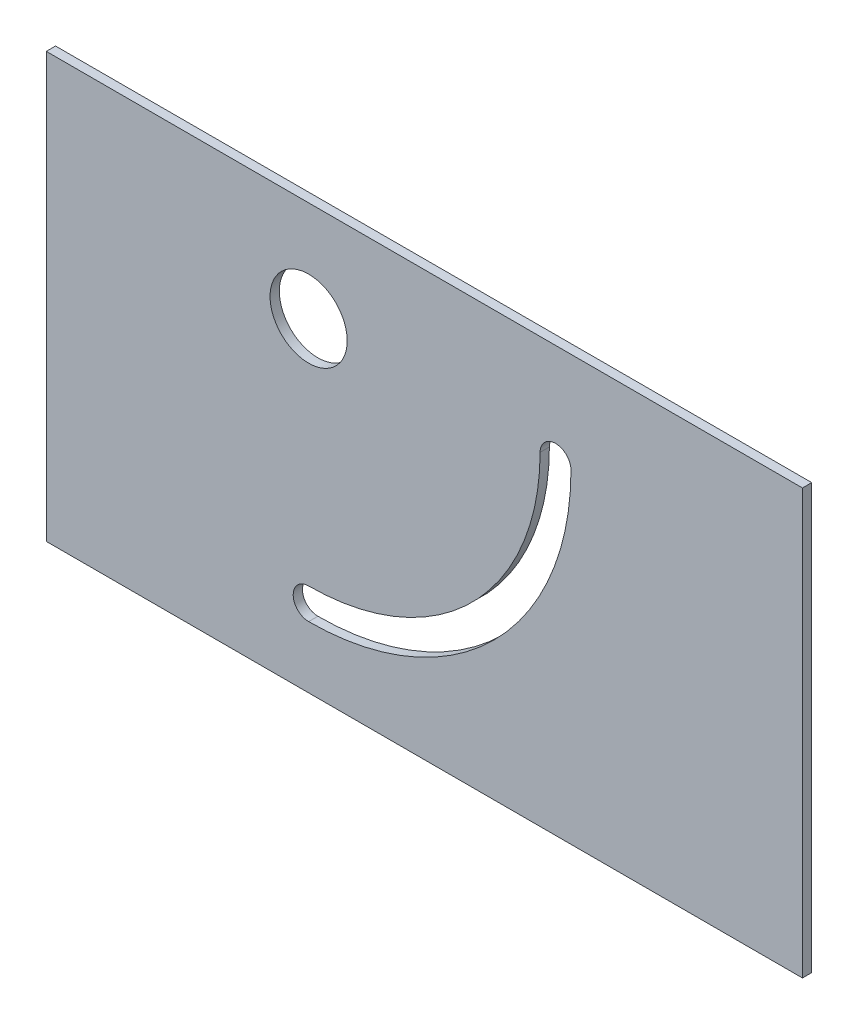
SolidWorks part; units mm, degrees
material "birch 3mm plywood"
ref_plane "Front Plane" through (0, 0, 0) normal (0, 0, 1) x (1, 0, 0)
ref_plane "Top Plane" through (0, 0, 0) normal (0, 1, 0) x (1, 0, 0)
ref_plane "Right Plane" through (0, 0, 0) normal (1, 0, 0) x (0, 0, -1)
sketch "Sketch1" plane through (0, 0, 0) normal (0, 0, 1) x (1, 0, 0)
  line L1 (-0.5, 137.5) -> (244.5, 137.5)
  line L2 (-0.5, 137.5) -> (-0.5, 0)
  line L3 (-0.5, 0) -> (244.5, 0)
  line L4 (244.5, 137.5) -> (244.5, 0)
  line L5 (84.5, 59.75) -> (84.5, -77.75) construction
  arc A3 (169.5, 105) -> (159.5, 105) centre (164.5, 105) ccw
  arc A4 (159.5, 105) -> (84.5, 30) centre (84.5, 105) cw
  arc A5 (169.5, 105) -> (84.5, 20) centre (84.5, 105) cw
  arc A6 (84.5, 20) -> (84.5, 30) centre (84.5, 25) cw
  circle A7 centre (84.5, 105) radius 12.5
  dimension "D1" = 10
  dimension "D2" = 75
  dimension "D3" = 20
  dimension "D7" = 25
  dimension "D4" = 20
  dimension "D5" = 85
  dimension "D6" = 160
extrude "Boss-Extrude1" add sketch "Sketch1" along normal blind 3
